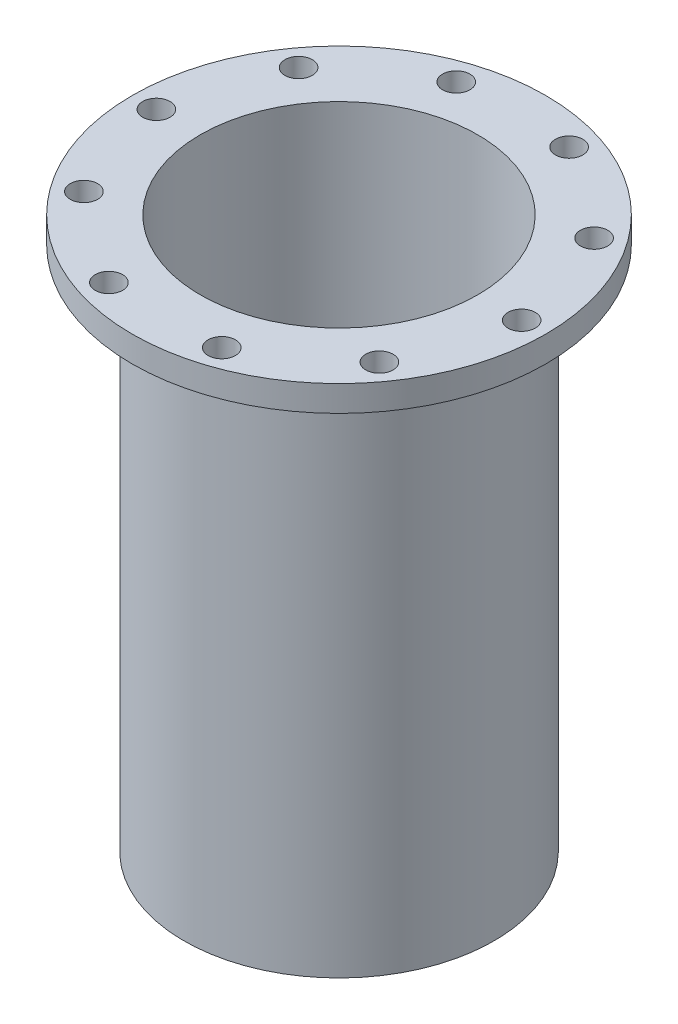
SolidWorks part; units mm, degrees
material "1023 Carbon Steel Sheet (SS)"
ref_plane "Front Plane" through (0, 0, 0) normal (0, 0, 1) x (1, 0, 0)
ref_plane "Top Plane" through (0, 0, 0) normal (0, 1, 0) x (1, 0, 0)
ref_plane "Right Plane" through (0, 0, 0) normal (1, 0, 0) x (0, 0, -1)
sketch "Sketch1" plane through (0, 0, 0) normal (0, 0, 1) x (1, 0, 0)
  line L0 (0, 0) -> (0, -134.8652) construction
  line L2 (51.1302, -203.2) -> (57.15, -203.2)
  line L3 (57.15, -203.2) -> (57.15, -9.525)
  line L4 (57.15, -9.525) -> (76.2, -9.525)
  line L5 (76.2, -9.525) -> (76.2, 0)
  line L6 (76.2, 0) -> (51.1302, 0)
  line L10 (51.1302, -185.42) -> (53.6702, -185.42)
  line L12 (51.1302, 0) -> (51.1302, -185.42)
  line L13 (53.6702, -185.42) -> (53.6702, -190.5)
  line L14 (53.6702, -190.5) -> (51.1302, -190.5)
  line L15 (51.1302, -190.5) -> (51.1302, -203.2)
  dimension "D1" = 51.1302
  dimension "D2" = 57.15
  dimension "D3" = 76.2
  dimension "D4" = 9.525
  dimension "D5" = 203.2
  dimension "D6" = 5.08
  dimension "D7" = 2.54
  dimension "D8" = 12.7
revolve "Revolve1" add sketch "Sketch1" angle 360 about L0 other way angle 360
hole_wizard "Tap Drill for 3/8-16 Tap1" positions "Sketch2" profile "Sketch3" hole size "3/8" standard "ANSI Inch" end condition through all
sketch "Sketch2" plane through (0, 0, 0) normal (0, 1, 0) x (1, 0, 0)
  point P1 (67.31, 0)
  dimension "D1" = 67.31
sketch "Sketch3" plane through (67.31, 0, 0) normal (1, 0, 0) x (0, 0, 1)
  line L0 (0, 0) -> (0, 203.2)
  line L1 (0, 203.2) -> (5.0419, 203.2)
  line L2 (5.0419, 203.2) -> (5.0419, 0)
  line L5 (5.0419, 0) -> (0, 0)
  line L11 (0, -6.35) -> (0, 107.95) construction
  dimension "Thru Hole Dia." = 10.0838
  dimension "Thru Hole Depth" = 203.2
pattern_circular "CirPattern1" count 10 over 360 about axis through (0, 0, 0) along (0, 1, 0) of "Tap Drill for 3/8-16 Tap1"
